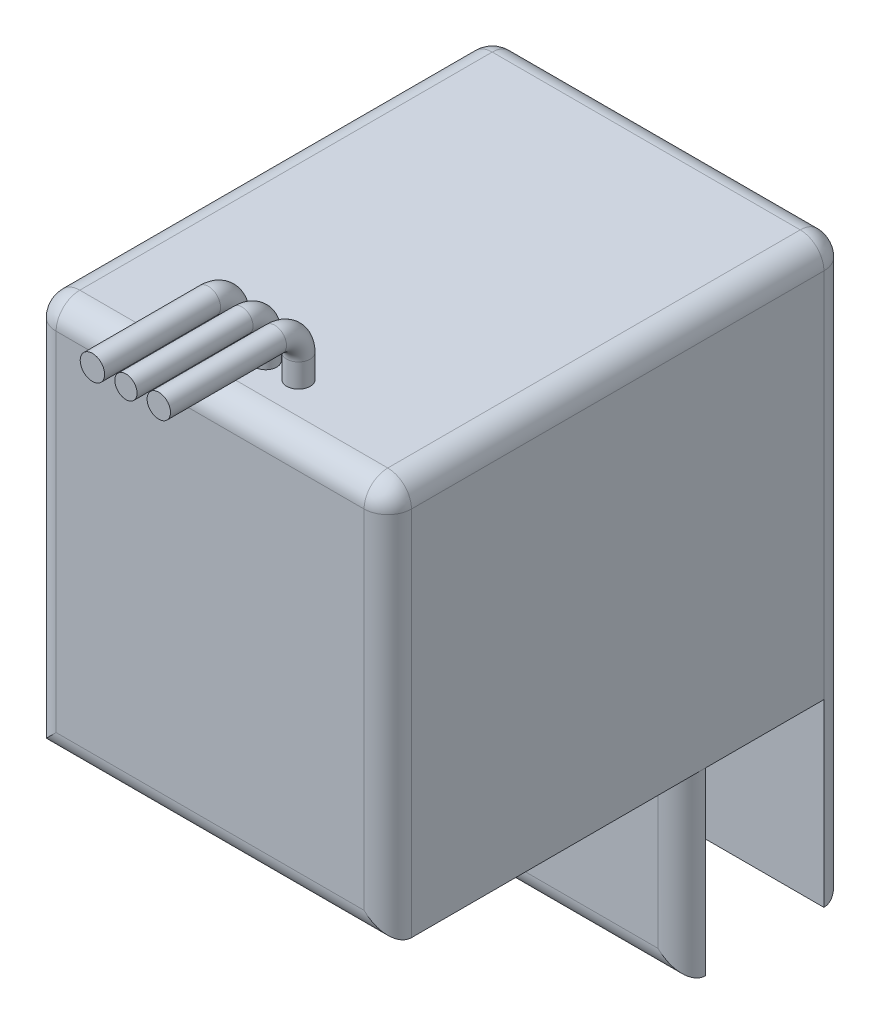
SolidWorks part; units mm, degrees
ref_plane "Front Plane" through (0, 0, 0) normal (0, 0, 1) x (1, 0, 0)
ref_plane "Top Plane" through (0, 0, 0) normal (0, 1, 0) x (1, 0, 0)
ref_plane "Right Plane" through (0, 0, 0) normal (1, 0, 0) x (0, 0, -1)
sketch "Sketch1" plane through (0, 0, 0) normal (0, 0, 1) x (1, 0, 0)
  line L1 (7.5, 12.5) -> (-7.5, 12.5)
  line L2 (7.5, 12.5) -> (7.5, -12.5)
  line L3 (7.5, -12.5) -> (-7.5, -12.5)
  line L4 (-7.5, 12.5) -> (-7.5, -12.5)
  line L5 (7.5, 12.5) -> (-7.5, -12.5) construction
  line L6 (7.5, -12.5) -> (-7.5, 12.5) construction
  point P0 (0, 0)
  dimension "D1" = 25
  dimension "D2" = 15
extrude "Boss-Extrude1" add sketch "Sketch1" along normal blind 30
sketch "Sketch2" plane through (0, 0, 0) normal (0, 0, -1) x (-1, 0, 0)
  line L0 (-7.5, -12.5) -> (7.5, -12.5)
  line L1 (7.5, -12.5) -> (7.5, -20.0971)
  line L2 (7.5, -20.0971) -> (-7.5, -20.0971)
  line L3 (-7.5, -20.0971) -> (-7.5, -12.5)
extrude "Boss-Extrude2" add sketch "Sketch2" against normal blind 1
ref_plane "Plane1" through (0, 0, 6) normal (0, 0, 1) x (1, 0, 0)
sketch "Sketch3" plane through (0, 0, 6) normal (0, 0, 1) x (1, 0, 0)
  line L0 (7.5, -12.5) -> (7.5, -20.0971)
  line L1 (7.5, -20.0971) -> (-7.5, -20.0971)
  line L2 (-7.5, -20.0971) -> (-7.5, -12.5)
  line L3 (-7.5, -12.5) -> (7.5, -12.5)
extrude "Boss-Extrude3" add sketch "Sketch3" along normal blind 1
sketch "Sketch4" plane through (7.5, 0, 0) normal (1, 0, 0) x (0, 0, -1)
  line L0 (0, 4.1708) -> (-19.4092, 4.1708)
  line L1 (0, -20.0971) -> (0, 12.5) construction
  line L2 (-19.4092, 4.1708) -> (-19.4092, -12.5)
  line L3 (-30, -12.5) -> (-7, -12.5) construction
  line L4 (-19.4092, -12.5) -> (-30, -12.5)
  line L5 (-30, -12.5) -> (-30, 12.5)
  line L6 (-30, 12.5) -> (0, 12.5)
  line L7 (0, 12.5) -> (0, 4.1708)
extrude "Cut-Extrude1" cut sketch "Sketch4" against normal blind 33
sketch "Sketch5" plane through (0, 0, 0) normal (0, 0, -1) x (-1, 0, 0)
  line L0 (-7.5083, -12.0431) -> (7.4404, -12.0431)
  line L1 (7.4404, -12.0431) -> (-7.5, 4.1708)
  circle A0 centre (-0.0298, -3.9362) radius 0.9044
extrude "Boss-Extrude4" add sketch "Sketch5" along normal blind 15 contours L1 A0 | L1 A0 region at (0.3121, -4.1963, 0) region at (-0.2525, -3.6761, 0)
sketch "Sketch6" plane through (0, 0, -15) normal (0, 0, -1) x (-1, 0, 0)
  line L1 (12.0069, 5.9788) -> (-12.0665, 5.9788)
  line L2 (12.0069, 5.9788) -> (12.0069, -13.8511)
  line L3 (12.0069, -13.8511) -> (-12.0665, -13.8511)
  line L4 (-12.0665, 5.9788) -> (-12.0665, -13.8511)
  line L5 (12.0069, 5.9788) -> (-12.0665, -13.8511) construction
  line L6 (12.0069, -13.8511) -> (-12.0665, 5.9788) construction
  point P0 (-0.0298, -3.9362)
extrude "Boss-Extrude5" add sketch "Sketch6" along normal blind 30
shell "Shell1" thickness 1 removed face at (0.0298, 5.9788, -30)
fillet "Fillet1" radius 3 8 edges at (-12.0069, -13.8511, -30) (0.0298, -13.8511, -45) (0.0298, -13.8511, -15) (12.0665, -13.8511, -30) (12.0665, -3.9362, -15) (-12.0069, -3.9362, -45) (12.0665, -3.9362, -45) (-12.0069, -3.9362, -15)
sketch "Sketch7" plane through (0, 5.9788, 0) normal (0, 1, 0) x (1, 0, 0)
  line L4 (-9.0069, 15) -> (9.0665, 15)
  line L5 (12.0665, 18) -> (12.0665, 42)
  line L6 (9.0665, 45) -> (-9.0069, 45)
  line L7 (-12.0069, 42) -> (-12.0069, 18)
  line L8 (-9.0069, 15) -> (9.0665, 15)
  line L9 (12.0665, 18) -> (12.0665, 42)
  line L10 (9.0665, 45) -> (-9.0069, 45)
  line L11 (-12.0069, 42) -> (-12.0069, 18)
  circle A0 centre (0, 21.7825) radius 5.385
  arc A4 (9.0665, 15) -> (12.0665, 18) centre (9.0665, 18) ccw
  arc A5 (12.0665, 42) -> (9.0665, 45) centre (9.0665, 42) ccw
  arc A6 (-9.0069, 45) -> (-12.0069, 42) centre (-9.0069, 42) ccw
  arc A7 (-12.0069, 18) -> (-9.0069, 15) centre (-9.0069, 18) ccw
  arc A8 (9.0665, 15) -> (12.0665, 18) centre (9.0665, 18) ccw
  arc A9 (12.0665, 42) -> (9.0665, 45) centre (9.0665, 42) ccw
  arc A10 (-9.0069, 45) -> (-12.0069, 42) centre (-9.0069, 42) ccw
  arc A11 (-12.0069, 18) -> (-9.0069, 15) centre (-9.0069, 18) ccw
  dimension "D1" = 0
extrude "Boss-Extrude6" add sketch "Sketch7" along normal blind 2
sketch "Sketch8" plane through (0, 7.9788, 0) normal (0, 1, 0) x (1, 0, 0)
  circle A0 centre (0, 21.7825) radius 6.7461
extrude "Boss-Extrude7" add sketch "Sketch8" along normal blind 1
sketch "Sketch9" plane through (0, 8.9788, 0) normal (0, 1, 0) x (1, 0, 0)
  line L0 (3.6045, 25.7436) -> (3.3145, 25.7436)
  line L1 (-3.6045, 25.7436) -> (-4.3595, 24.8933)
  line L2 (-4.3595, 24.8933) -> (-2.7538, 24.8933)
  line L3 (4.3595, 24.8933) -> (3.6045, 25.7436)
  line L4 (5.2562, 22.8094) -> (3.3145, 22.8094)
  line L5 (-5.2562, 22.8094) -> (-5.3556, 21.7825)
  line L6 (-5.3556, 21.7825) -> (-2.7538, 21.7825)
  line L7 (5.3556, 21.7825) -> (5.2562, 22.8094)
  line L8 (4.8045, 19.3506) -> (3.3145, 19.3506)
  line L9 (-4.7716, 19.3506) -> (-4.0047, 18.2265)
  line L10 (-4.0047, 18.2265) -> (-2.7538, 18.2265)
  line L11 (4.0047, 18.2265) -> (4.8045, 19.3506)
  line L12 (0.7789, 27.0812) -> (0.7789, 25.7436)
  line L13 (0.7789, 16.4839) -> (0, 16.4269)
  line L14 (0, 16.4269) -> (0, 18.2265)
  line L15 (0, 27.1381) -> (0.7789, 27.0812)
  line L16 (-2.0798, 26.7178) -> (-2.0798, 25.7436)
  line L17 (-2.0798, 16.8473) -> (-2.7538, 17.1892)
  line L18 (-2.7538, 17.1892) -> (-2.7538, 18.2265)
  line L19 (-2.7538, 26.3759) -> (-2.0798, 26.7178)
  line L24 (2.4462, 26.5468) -> (2.4462, 25.7436)
  line L25 (2.4462, 17.0182) -> (3.3145, 17.5758)
  line L26 (3.3145, 17.5758) -> (3.3145, 18.2265)
  line L27 (3.3145, 25.9892) -> (2.4462, 26.5468)
  line L32 (3.3145, 25.7436) -> (3.3145, 25.9892)
  line L33 (2.4462, 25.7436) -> (0.7789, 25.7436)
  line L34 (-4.2933, 19.3506) -> (-4.7716, 19.3506)
  line L35 (2.4462, 24.8933) -> (2.4462, 22.8094)
  line L36 (3.3145, 24.8933) -> (4.3595, 24.8933)
  line L37 (3.3145, 22.8094) -> (3.3145, 24.8933)
  line L38 (2.4462, 21.7825) -> (2.4462, 19.3506)
  line L39 (2.4462, 22.8094) -> (0.7789, 22.8094)
  line L40 (3.3145, 21.7825) -> (5.3556, 21.7825)
  line L41 (3.3145, 19.3506) -> (3.3145, 21.7825)
  line L42 (3.3145, 18.2265) -> (4.0047, 18.2265)
  line L43 (2.4462, 18.2265) -> (2.4462, 17.0182)
  line L44 (2.4462, 19.3506) -> (0.7789, 19.3506)
  line L45 (0.7789, 18.2265) -> (0.7789, 16.4839)
  line L46 (0, 19.3506) -> (-2.0798, 19.3506)
  line L47 (0.7789, 18.2265) -> (2.4462, 18.2265)
  line L48 (0, 19.3506) -> (0, 21.7825)
  line L49 (-2.0798, 18.2265) -> (-2.0798, 16.8473)
  line L50 (-2.7538, 19.3506) -> (-4.7716, 19.3506)
  line L51 (-2.7538, 19.3506) -> (-2.7538, 21.7825)
  line L52 (-2.0798, 18.2265) -> (0, 18.2265)
  line L53 (-2.0798, 21.7825) -> (-2.0798, 19.3506)
  line L54 (-2.7538, 22.8094) -> (-5.2562, 22.8094)
  line L55 (-2.7538, 22.8094) -> (-2.7538, 24.8933)
  line L56 (-2.0798, 21.7825) -> (0, 21.7825)
  line L57 (0.7789, 21.7825) -> (0.7789, 19.3506)
  line L58 (0, 22.8094) -> (-2.0798, 22.8094)
  line L59 (0.7789, 21.7825) -> (2.4462, 21.7825)
  line L60 (0, 22.8094) -> (0, 24.8933)
  line L61 (0.7789, 24.8933) -> (2.4462, 24.8933)
  line L62 (0.7789, 24.8933) -> (0.7789, 22.8094)
  line L63 (0, 25.7436) -> (-2.0798, 25.7436)
  line L64 (0, 25.7436) -> (0, 27.1381)
  line L65 (-2.0798, 24.8933) -> (0, 24.8933)
  line L66 (-2.7538, 25.7436) -> (-3.6045, 25.7436)
  line L67 (-2.7538, 25.7436) -> (-2.7538, 26.3759)
  line L68 (-2.0798, 24.8933) -> (-2.0798, 22.8094)
  circle A1 centre (0, 21.7825) radius 5.385 construction
extrude "Boss-Extrude10" add sketch "Sketch9" along normal blind 1 separate body contours L67 L66 L1 L2 L55 L54 L5 L6 L51 L50 L34 L9 L10 L18 L17 L49 L52 L14 L13 L45 L47 L43 L25 L26 L42 L11 L8 L41 L40 L7 L4 L37 L36 L3 L0 L32 L27 L24 L33 L12 L15 L64 L63 L16 L19 L68 L65 L60 L58 region at (0.1544, 8.9788, -21.7736)
sketch "Sketch10" plane through (0, 8.9788, 0) normal (0, 1, 0) x (1, 0, 0)
  circle A0 centre (0, 21.7825) radius 5.385 construction
  circle A3 centre (0, 21.7825) radius 5.385
extrude "Cut-Extrude2" cut sketch "Sketch10" against normal blind 11
sketch "Sketch11" plane through (0, 8.9788, 0) normal (0, 1, 0) x (1, 0, 0)
  circle A0 centre (0, 21.7825) radius 5.385
  circle A1 centre (0, 21.7825) radius 6.1056
extrude "Boss-Extrude11" add sketch "Sketch11" along normal blind 3
fillet "Fillet2" radius 3 8 edges at (-11.1282, 7.9788, -44.1213) (0.0298, 7.9788, -45) (11.1878, 7.9788, -44.1213) (12.0665, 7.9788, -30) (11.1878, 7.9788, -15.8787) (0.0298, 7.9788, -15) (-11.1282, 7.9788, -15.8787) (-12.0069, 7.9788, -30)
fillet "Fillet3" radius 0.2 4 edges at (0, 8.9788, -15.677) (0, 11.9788, -16.3976) (0, 11.9788, -15.677) (0, 8.9788, -15.0364)
fillet "Fillet4" radius 1 13 edges at (-7.5, -16.2985, 7) (7.5, -16.2985, 7) (0, -20.0971, 7) (0, -12.5, 19.4092) (7.5, -4.1646, 19.4092) (-7.5, -4.1646, 19.4092) (7.5, -7.9631, 0) (0, -20.0971, 0) (-7.5, -7.9631, 0) (0, 4.1708, 19.4092) (7.5, 4.1708, 9.7046) (0, 4.1708, 0) (-7.5, 4.1708, 9.7046)
sketch "Sketch12" plane through (0, 0, 7) normal (0, 0, 1) x (1, 0, 0)
  line L1 (-0.7307, -16.9767) -> (0.7582, -16.9609)
  line L2 (0.7582, -16.9609) -> (1.4889, -15.6635)
  line L3 (1.4889, -15.6635) -> (0.7307, -14.382)
  line L4 (0.7307, -14.382) -> (-0.7582, -14.3978)
  line L5 (-0.7582, -14.3978) -> (-1.4889, -15.6952)
  line L6 (-1.4889, -15.6952) -> (-0.7307, -16.9767)
  circle A0 centre (0, -15.6793) radius 1.2895 construction
extrude "Boss-Extrude12" add sketch "Sketch12" along normal blind 1
sketch "Sketch13" plane through (0, 0, 8) normal (0, 0, 1) x (1, 0, 0)
  circle A0 centre (0, -15.6275) radius 0.6395
extrude "Boss-Extrude13" add sketch "Sketch13" along normal blind 5
sketch "Sketch14" plane through (0, 0, 13) normal (0, 0, 1) x (1, 0, 0)
  line L1 (-0.8844, -17.1379) -> (0.8659, -17.1486)
  line L2 (0.8659, -17.1486) -> (1.7503, -15.6382)
  line L3 (1.7503, -15.6382) -> (0.8844, -14.117)
  line L4 (0.8844, -14.117) -> (-0.8659, -14.1063)
  line L5 (-0.8659, -14.1063) -> (-1.7503, -15.6167)
  line L6 (-1.7503, -15.6167) -> (-0.8844, -17.1379)
  circle A0 centre (0, -15.6275) radius 1.5158 construction
extrude "Boss-Extrude14" add sketch "Sketch14" along normal blind 1
sketch "Sketch15" plane through (12.0665, 0, 0) normal (1, 0, 0) x (0, 0, -1)
  line L0 (2.3621, 17.6699) -> (50.3218, 17.6699)
  line L1 (50.3218, 17.6699) -> (50.3218, -23.1495)
  line L2 (50.3218, -23.1495) -> (2.3621, -23.1495)
  line L3 (2.3621, -23.1495) -> (2.3621, 17.6699)
extrude "Cut-Extrude4" cut sketch "Sketch15" against normal blind 68
sketch "Sketch16" plane through (0, 4.1708, 0) normal (0, 1, 0) x (1, 0, 0)
  circle A1 centre (0, -17.0648) radius 0.4706
  circle A2 centre (1.3859, -17.0648) radius 0.4941
  circle A3 centre (-1.416, -17.0648) radius 0.5148
sketch "Sketch17" plane through (0, 0, 0) normal (1, 0, 0) x (0, 0, -1)
  line L0 (-17.0648, 4.1708) -> (-17.0648, 5.1661)
  line L1 (-16.5707, 4.1708) -> (-17.5589, 4.1708) construction
  line L2 (-18.0648, 6.1661) -> (-22.9613, 6.1661)
  arc A0 (-18.0648, 6.1661) -> (-17.0648, 5.1661) centre (-18.0648, 5.1661) cw
  dimension "D1" = 1
sweep "Sweep1" add profiles "Sketch16" path "Sketch17"
